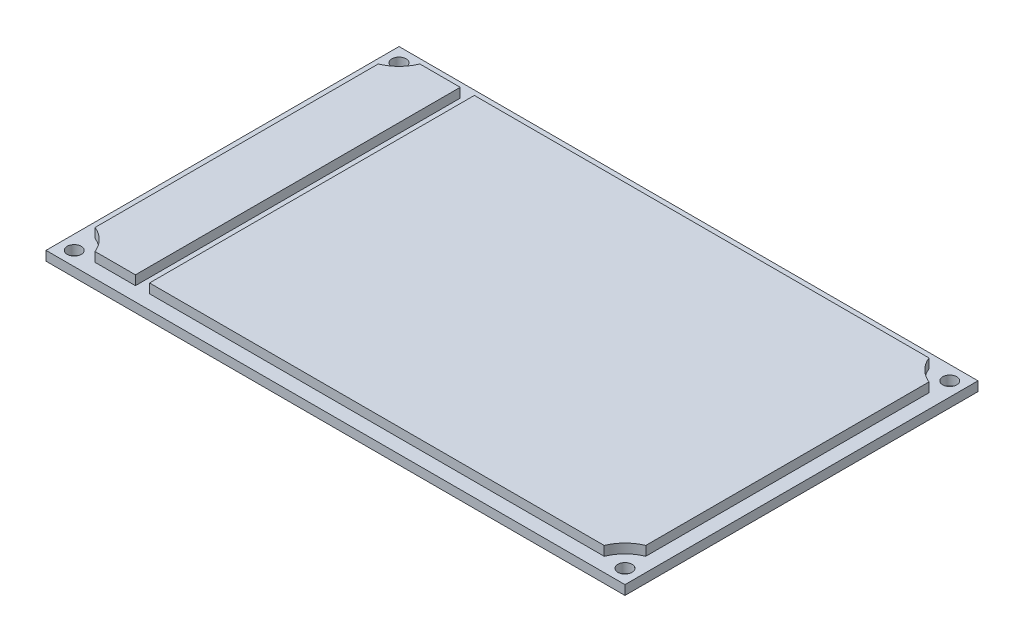
SolidWorks part; units mm, degrees
ref_plane "Спереди" through (0, 0, 0) normal (0, 0, 1) x (1, 0, 0)
ref_plane "Сверху" through (0, 0, 0) normal (0, 1, 0) x (1, 0, 0)
ref_plane "Справа" through (0, 0, 0) normal (1, 0, 0) x (0, 0, -1)
sketch "Эскиз1" plane through (0, 0, 0) normal (0, 1, 0) x (1, 0, 0)
  line L0 (-62.7105, 38.0423) -> (60.2895, 38.0423)
  line L1 (-62.7105, 38.0423) -> (-62.7105, -36.9577)
  line L2 (-62.7105, -36.9577) -> (60.2895, -36.9577)
  line L3 (60.2895, 38.0423) -> (60.2895, -36.9577)
  line L4 (-46.7105, 35.0423) -> (-55.2943, 35.0423)
  line L5 (-46.7105, 35.0423) -> (-46.7105, -33.9577)
  line L6 (-46.7105, -33.9577) -> (-55.2943, -33.9577)
  line L7 (-59.7105, 30.6261) -> (-59.7105, -29.5415)
  line L8 (-43.7105, 35.0423) -> (52.8733, 35.0423)
  line L9 (-43.7105, 35.0423) -> (-43.7105, -33.9577)
  line L10 (-43.7105, -33.9577) -> (52.8733, -33.9577)
  line L11 (57.2895, 30.6261) -> (57.2895, -29.5415)
  arc A0 (-59.7105, 30.6261) -> (-55.2943, 35.0423) centre (-62.7105, 38.0423) ccw
  arc A1 (-55.2943, -33.9577) -> (-59.7105, -29.5415) centre (-62.7105, -36.9577) ccw
  arc A2 (57.2895, -29.5415) -> (52.8733, -33.9577) centre (60.2895, -36.9577) ccw
  arc A3 (52.8733, 35.0423) -> (57.2895, 30.6261) centre (60.2895, 38.0423) ccw
  circle A4 centre (-59.7105, 35.0423) radius 1.5
  circle A5 centre (-59.7105, -33.9577) radius 1.5
  circle A6 centre (57.2895, -33.9577) radius 1.5
  circle A7 centre (57.2895, 35.0423) radius 1.5
  point P24 (0, 0)
  point P25 (0, 0)
  point P26 (0, 0)
  point P27 (0, 0)
  point P28 (0, 0)
  point P29 (0, 0)
  point P30 (0, 0)
extrude "Бобышка-Вытянуть1" add sketch "Эскиз1" along normal blind 2 contours L5 L6 A1 L7 A0 L4
extrude "Бобышка-Вытянуть2" add sketch "Эскиз1<4>" along normal blind 2 separate body contours L9 L10 A2 L11 A3 L8
sketch "Эскиз1<4>" plane through (0, 0, 0) normal (0, 1, 0) x (1, 0, 0) same geometry as "Эскиз1"
extrude "Бобышка-Вытянуть3" add sketch "Эскиз1<5>" against normal blind 2 contours L0 L3 L2 L1
sketch "Эскиз1<5>" plane through (0, 0, 0) normal (0, 1, 0) x (1, 0, 0) same geometry as "Эскиз1"
extrude "Вырез-Вытянуть1" cut sketch "Эскиз1<6>" against normal blind 12 contours A6 | A7 | A5 | A4
sketch "Эскиз1<6>" plane through (0, 0, 0) normal (0, 1, 0) x (1, 0, 0) same geometry as "Эскиз1"
